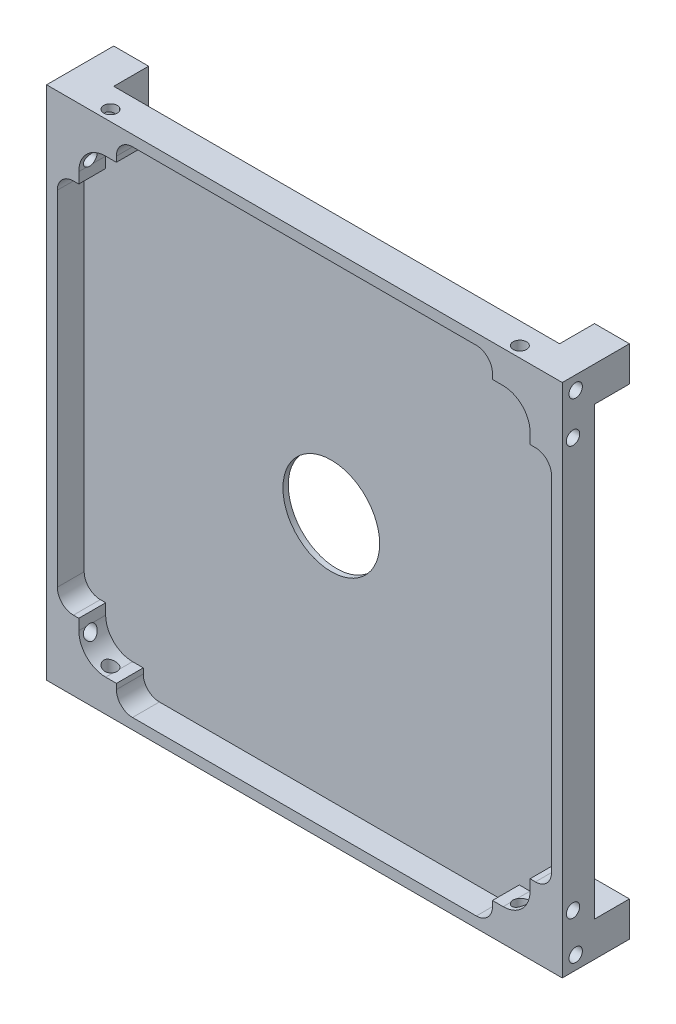
SolidWorks part; units mm, degrees
material "7075-T6 (SN)"
ref_plane "Front Plane" through (0, 0, 0) normal (0, 0, 1) x (1, 0, 0)
ref_plane "Top Plane" through (0, 0, 0) normal (0, 1, 0) x (1, 0, 0)
ref_plane "Right Plane" through (0, 0, 0) normal (1, 0, 0) x (0, 0, -1)
sketch "Sketch1" plane through (0, 0, 0) normal (0, 0, 1) x (1, 0, 0)
  line L1 (48, -48) -> (-48, -48)
  line L2 (48, -48) -> (48, 48)
  line L3 (48, 48) -> (-48, 48)
  line L4 (-48, -48) -> (-48, 48)
  line L5 (48, -48) -> (-48, 48) construction
  line L6 (48, 48) -> (-48, -48) construction
  point P0 (0, 0)
  dimension "D1" = 96
  dimension "D2" = 96
extrude "Boss-Extrude1" add sketch "Sketch1" along normal blind 2
sketch "Sketch2" plane through (0, 0, 2) normal (0, 0, 1) x (1, 0, 0)
  line L0 (48, 48) -> (-48, 48) construction
  line L1 (37, -42) -> (-37, -42)
  line L2 (42, -37) -> (42, 37)
  line L3 (37, 42) -> (-37, 42)
  line L4 (-42, -37) -> (-42, 37)
  line L5 (42, -42) -> (-42, 42) construction
  line L6 (42, 42) -> (-42, -42) construction
  line L7 (48, -48) -> (48, 48) construction
  line L12 (-48, 48) -> (-48, -48)
  line L13 (-48, -48) -> (48, -48)
  line L14 (48, -48) -> (48, 48)
  line L15 (48, 48) -> (-48, 48)
  line L16 (-48, 48) -> (-48, -48)
  line L17 (-48, -48) -> (48, -48)
  line L18 (48, -48) -> (48, 48)
  line L19 (48, 48) -> (-48, 48)
  arc A0 (-37, -42) -> (-42, -37) centre (-37, -37) cw
  arc A1 (37, -42) -> (42, -37) centre (37, -37) ccw
  arc A2 (42, 37) -> (37, 42) centre (37, 37) ccw
  arc A3 (-37, 42) -> (-42, 37) centre (-37, 37) ccw
  point P0 (0, 0)
  dimension "D4" = 5
  dimension "D1" = 6
  dimension "D2" = 6
extrude "Boss-Extrude2" add sketch "Sketch2" along normal blind 5
sketch "Sketch4" plane through (0, 0, 7) normal (0, 0, 1) x (1, 0, 0)
  line L0 (-41.5, 41.5) -> (41.5, -41.5) construction
  line L1 (-41.5, 41.5) -> (41.5, 41.5)
  line L2 (-41.5, 41.5) -> (-41.5, -41.5)
  line L3 (-41.5, -41.5) -> (41.5, -41.5)
  line L4 (41.5, 41.5) -> (41.5, -41.5)
  point P4 (0, 0)
  dimension "D1" = 83
  dimension "D2" = 83
sketch "Sketch3" plane through (0, 0, 0) normal (0, 0, -1) x (-1, 0, 0)
  line L1 (-48, 48) -> (-41.5, 48)
  line L2 (-48, 48) -> (-48, 41.5)
  line L3 (-48, 41.5) -> (-41.5, 41.5)
  line L4 (-41.5, 48) -> (-41.5, 41.5)
  line L5 (48, 48) -> (41.5, 48)
  line L6 (48, 48) -> (48, 41.5)
  line L7 (48, 41.5) -> (41.5, 41.5)
  line L8 (41.5, 48) -> (41.5, 41.5)
  line L9 (-48, -48) -> (-41.5, -48)
  line L10 (-48, -48) -> (-48, -41.5)
  line L11 (-48, -41.5) -> (-41.5, -41.5)
  line L12 (-41.5, -48) -> (-41.5, -41.5)
  line L13 (48, -48) -> (41.5, -48)
  line L14 (48, -48) -> (48, -41.5)
  line L15 (48, -41.5) -> (41.5, -41.5)
  line L16 (41.5, -48) -> (41.5, -41.5)
  dimension "D1" = 6.5
  dimension "D2" = 6.5
  dimension "D3" = 6.5
  dimension "D4" = 6.5
extrude "Boss-Extrude3" add sketch "Sketch3" along normal blind 6.5
sketch "Sketch5" plane through (0, 0, 0) normal (0, 0, -1) x (-1, 0, 0)
  circle A0 centre (0, 0) radius 9
  dimension "D1" = 18
extrude "Cut-Extrude1" cut sketch "Sketch5" against normal blind 10
sketch "Sketch6" plane through (-48, 0, 0) normal (-1, 0, 0) x (0, 0, 1)
  line L0 (-6.5, -45.5) -> (7, -45.5) construction
  line L2 (7, 48) -> (7, -48) construction
  line L3 (-6.5, 45.5) -> (7, 45.5) construction
  line L5 (7, 48) -> (-6.5, 48) construction
  line L6 (7, -48) -> (-6.5, -48) construction
  point P6 (3.5, -45.5)
  point P11 (3.5, 45.5)
  dimension "D1" = 3.5
  dimension "D2" = 3.5
  dimension "D3" = 2.5
  dimension "D4" = 2.5
hole_wizard "M3 Tapped Hole1" positions "3DSketch1" profile "Sketch7" tap size "M3" standard "ISO"
sketch3d "3DSketch1"
  point P0 (-48, 45.5, 3.5)
  point P3 (-48, -45.5, 3.5)
sketch "Sketch7" plane through (-48, 45.5, 3.5) normal (0, 1, 0) x (0, 0, 1)
  line L0 (0, 0) -> (0, 10.2511)
  line L1 (0, 10.2511) -> (1.25, 9.5)
  line L2 (1.25, 9.5) -> (1.25, 0)
  line L5 (1.25, 0) -> (0, 0)
  line L10 (0, 10.2511) -> (-1.25, 9.5) construction
  line L11 (0, -6.35) -> (0, 107.95) construction
  dimension "Tap Drill Dia." = 2.5
  dimension "Tap Drill Depth" = 9.5
  dimension "Drill Angle" = 118
cosmetic thread "Hole Thread1" parameters "D1"=8, "D2"=3
cosmetic thread "Hole Thread2" parameters "D1"=8, "D2"=3
mirror "Mirror1" about plane through (0, 0, 0) normal (1, 0, 0) of "M3 Tapped Hole1"
sketch "Sketch8" plane through (48, 0, 0) normal (1, 0, 0) x (0, 0, -1)
  point P0 (-4, -38.0996)
  point P1 (-4, 38.1004)
hole_wizard "M3 Tapped Hole2" positions "3DSketch2" profile "Sketch10" tap size "M3" standard "ISO"
sketch3d "3DSketch2"
  point P0 (48, 38.1004, 4)
  point P3 (48, -38.0996, 4)
sketch "Sketch10" plane through (48, 38.1004, 4) normal (0, 1, 0) x (0, 0, -1)
  line L0 (0, 0) -> (0, 9.2511)
  line L1 (0, 9.2511) -> (1.25, 8.5)
  line L2 (1.25, 8.5) -> (1.25, 0)
  line L5 (1.25, 0) -> (0, 0)
  line L10 (0, 9.2511) -> (-1.25, 8.5) construction
  line L11 (0, -6.35) -> (0, 107.95) construction
  dimension "Tap Drill Dia." = 2.5
  dimension "Tap Drill Depth" = 8.5
  dimension "Drill Angle" = 118
cosmetic thread "Hole Thread3" parameters "D1"=6, "D2"=3
cosmetic thread "Hole Thread4" parameters "D1"=6, "D2"=3
ref_axis "Axis1" through (0, 0, 2) along (0, 0, -1)
pattern_circular "CirPattern1" count 4 every 90 about axis through (0, 0, 2) along (0, 0, -1) of "M3 Tapped Hole2"
sketch "Sketch11" plane through (0, 0, 7) normal (0, 0, 1) x (1, 0, 0)
  line L0 (-37, -42) -> (37, -42) construction
  line L1 (32, -46) -> (-32, -46)
  line L2 (35, -43) -> (35, -42)
  line L3 (35, -42) -> (-35, -42)
  line L4 (-35, -43) -> (-35, -42)
  line L5 (-48, -48) -> (48, -48) construction
  line L6 (48, -48) -> (48, 48) construction
  line L7 (-48, 48) -> (-48, -48) construction
  line L8 (48, 48) -> (-48, 48) construction
  line L9 (-42, -35) -> (-43, -35)
  line L10 (-42, -35) -> (-42, 35)
  line L11 (-42, 35) -> (-43, 35)
  line L12 (-37, -42) -> (37, -42)
  line L13 (42, -37) -> (42, 37)
  line L14 (37, 42) -> (-37, 42)
  line L15 (-42, 37) -> (-42, -37)
  line L16 (-37, -42) -> (37, -42)
  line L17 (42, -37) -> (42, 37)
  line L18 (37, 42) -> (-37, 42)
  line L19 (-42, 37) -> (-42, -37)
  line L20 (-46, -32) -> (-46, 32)
  arc A0 (-43, 35) -> (-46, 32) centre (-43, 32) ccw
  arc A1 (-43, -35) -> (-46, -32) centre (-43, -32) cw
  arc A2 (-32, -46) -> (-35, -43) centre (-32, -43) cw
  arc A3 (32, -46) -> (35, -43) centre (32, -43) ccw
  arc A4 (-42, -37) -> (-37, -42) centre (-37, -37) ccw
  arc A5 (37, -42) -> (42, -37) centre (37, -37) ccw
  arc A6 (42, 37) -> (37, 42) centre (37, 37) ccw
  arc A7 (-37, 42) -> (-42, 37) centre (-37, 37) ccw
  arc A8 (-42, -37) -> (-37, -42) centre (-37, -37) ccw
  arc A9 (37, -42) -> (42, -37) centre (37, -37) ccw
  arc A10 (42, 37) -> (37, 42) centre (37, 37) ccw
  arc A11 (-37, 42) -> (-42, 37) centre (-37, 37) ccw
  point P10 (-35, -42.5)
  line M21 (37, -42) -> (-37, -42)
  line M23 (-42, -37) -> (-42, 37)
  dimension "D1" = 2
  dimension "D8" = 3
  dimension "D2" = 13
  dimension "D3" = 13
  dimension "D5" = 13
  dimension "D6" = 13
  dimension "D7" = 2
extrude "Cut-Extrude2" cut sketch "Sketch11" against normal up to surface (5 mm away) contours A1 L9 L11 A0 L20 M23 | L1 A3 L2 L4 A2 M21 region at (0, -43.9814, 7) region at (-43.9814, 0, 7) up to face at (9, 0, 2)
pattern_circular "CirPattern2" count 2 every 180 about axis through (0, 0, 2) along (0, 0, -1) of "Cut-Extrude2"
sketch "Sketch12" plane through (0, 0, 2) normal (0, 0, 1) x (1, 0, 0)
  line L20 (-37, -42) -> (-35, -42)
  line L21 (-35, -42) -> (-35, -43)
  line L22 (-32, -46) -> (32, -46)
  line L23 (35, -43) -> (35, -42)
  line L24 (35, -42) -> (37, -42)
  line L25 (42, -37) -> (42, -35)
  line L26 (42, -35) -> (43, -35)
  line L27 (46, -32) -> (46, 32)
  line L28 (43, 35) -> (42, 35)
  line L29 (42, 35) -> (42, 37)
  line L30 (37, 42) -> (35, 42)
  line L31 (35, 42) -> (35, 43)
  line L32 (32, 46) -> (-32, 46)
  line L33 (-35, 43) -> (-35, 42)
  line L34 (-35, 42) -> (-37, 42)
  line L35 (-42, 37) -> (-42, 35)
  line L36 (-42, 35) -> (-43, 35)
  line L37 (-46, 32) -> (-46, -32)
  line L38 (-43, -35) -> (-42, -35)
  line L39 (-42, -35) -> (-42, -37)
  line L40 (-37, -42) -> (-35, -42)
  line L41 (-35, -42) -> (-35, -43)
  line L42 (-32, -46) -> (32, -46)
  line L43 (35, -43) -> (35, -42)
  line L44 (35, -42) -> (37, -42)
  line L45 (42, -37) -> (42, -35)
  line L46 (42, -35) -> (43, -35)
  line L47 (46, -32) -> (46, 32)
  line L48 (43, 35) -> (42, 35)
  line L49 (42, 35) -> (42, 37)
  line L50 (37, 42) -> (35, 42)
  line L51 (35, 42) -> (35, 43)
  line L52 (32, 46) -> (-32, 46)
  line L53 (-35, 43) -> (-35, 42)
  line L54 (-35, 42) -> (-37, 42)
  line L55 (-42, 37) -> (-42, 35)
  line L56 (-42, 35) -> (-43, 35)
  line L57 (-46, 32) -> (-46, -32)
  line L58 (-43, -35) -> (-42, -35)
  line L59 (-42, -35) -> (-42, -37)
  arc A12 (-42, -37) -> (-37, -42) centre (-37, -37) ccw
  arc A13 (-35, -43) -> (-32, -46) centre (-32, -43) ccw
  arc A14 (32, -46) -> (35, -43) centre (32, -43) ccw
  arc A15 (37, -42) -> (42, -37) centre (37, -37) ccw
  arc A16 (43, -35) -> (46, -32) centre (43, -32) ccw
  arc A17 (46, 32) -> (43, 35) centre (43, 32) ccw
  arc A18 (42, 37) -> (37, 42) centre (37, 37) ccw
  arc A19 (35, 43) -> (32, 46) centre (32, 43) ccw
  arc A20 (-32, 46) -> (-35, 43) centre (-32, 43) ccw
  arc A21 (-37, 42) -> (-42, 37) centre (-37, 37) ccw
  arc A22 (-43, 35) -> (-46, 32) centre (-43, 32) ccw
  arc A23 (-46, -32) -> (-43, -35) centre (-43, -32) ccw
  arc A24 (-42, -37) -> (-37, -42) centre (-37, -37) ccw
  arc A25 (-35, -43) -> (-32, -46) centre (-32, -43) ccw
  arc A26 (32, -46) -> (35, -43) centre (32, -43) ccw
  arc A27 (37, -42) -> (42, -37) centre (37, -37) ccw
  arc A28 (43, -35) -> (46, -32) centre (43, -32) ccw
  arc A29 (46, 32) -> (43, 35) centre (43, 32) ccw
  arc A30 (42, 37) -> (37, 42) centre (37, 37) ccw
  arc A31 (35, 43) -> (32, 46) centre (32, 43) ccw
  arc A32 (-32, 46) -> (-35, 43) centre (-32, 43) ccw
  arc A33 (-37, 42) -> (-42, 37) centre (-37, 37) ccw
  arc A34 (-43, 35) -> (-46, 32) centre (-43, 32) ccw
  arc A35 (-46, -32) -> (-43, -35) centre (-43, -32) ccw
  dimension "D1" = 0
extrude "Cut-Extrude3" cut sketch "Sketch12" against normal blind 1
sketch "Sketch13" plane through (0, 0, 7) normal (0, 0, 1) x (1, 0, 0)
  line L4 (48, 48) -> (-48, 48)
  line L5 (-48, 48) -> (-48, -48)
  line L6 (-48, -48) -> (48, -48)
  line L7 (48, -48) -> (48, 48)
  line L8 (48, 48) -> (-48, 48)
  line L9 (-48, 48) -> (-48, -48)
  line L10 (-48, -48) -> (48, -48)
  line L11 (48, -48) -> (48, 48)
  dimension "D1" = 0
extrude "Cut-Extrude4" cut sketch "Sketch13" against normal blind 1
sketch "Sketch14" plane through (0, 0, 0) normal (0, 0, -1) x (-1, 0, 0)
  circle A0 centre (0, 0) radius 20
  text T0 "MSSG       -      EYE-SAT" font "Impact" height 4
  dimension "D1" = 40
equation "\"D2@Sketch1\"=\"D1@Sketch1\""
equation "\"thickness\" = 2"
equation "\"D1@Boss-Extrude1\"=\"thickness\""
equation "\"D2@Sketch2\"=\"D1@Sketch2\""
equation "\"D2@Sketch3\"=\"D1@Sketch3\""
equation "\"D3@Sketch3\"=\"D1@Sketch3\""
equation "\"D4@Sketch3\"=\"D1@Sketch3\""
equation "\"D2@Sketch4\"=\"D1@Sketch4\""
equation "\"D2@Sketch6\"=\"D1@Sketch6\""
equation "\"D4@Sketch6\"=\"D3@Sketch6\""
equation "\"D3@Sketch11\"=\"D2@Sketch11\""
equation "\"D5@Sketch11\"=\"D2@Sketch11\""
equation "\"D6@Sketch11\"=\"D2@Sketch11\""
equation "\"D7@Sketch11\"=\"D1@Sketch11\""
